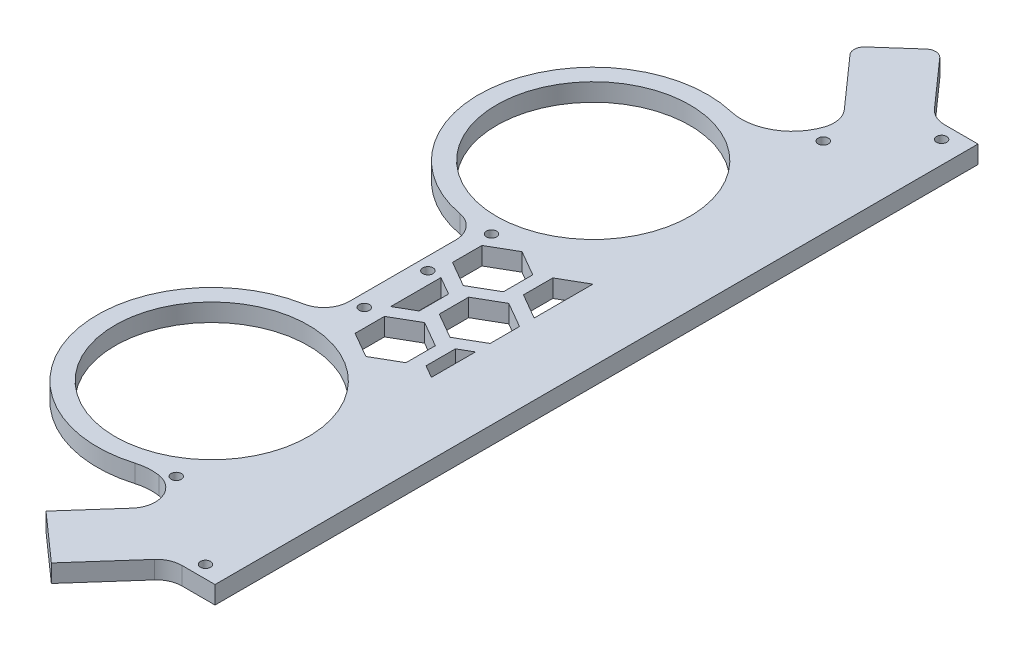
SolidWorks part; units mm, degrees
ref_plane "Front Plane" through (0, 0, 0) normal (0, 0, 1) x (1, 0, 0)
ref_plane "Top Plane" through (0, 0, 0) normal (0, 1, 0) x (1, 0, 0)
ref_plane "Right Plane" through (0, 0, 0) normal (1, 0, 0) x (0, 0, -1)
sketch "Sketch4" plane through (0, 0, 0) normal (0, 1, 0) x (1, 0, 0)
  line L0 (-171.45, -234.95) -> (-171.45, 190.5) construction
  line L1 (-127, -190.5) -> (127, -190.5) construction
  line L2 (-127, -190.5) -> (-127, 190.5) construction
  line L3 (-127, 190.5) -> (127, 190.5) construction
  line L4 (127, -190.5) -> (127, 190.5) construction
  line L5 (-127, -190.5) -> (127, 190.5) construction
  line L6 (-127, 190.5) -> (127, -190.5) construction
  line L8 (171.45, -234.95) -> (171.45, 190.5) construction
  line L9 (-171.45, -234.95) -> (171.45, -234.95) construction
  line L10 (-171.45, 190.5) -> (171.45, 190.5) construction
  line L12 (-171.45, -234.95) -> (-171.45, 234.95) construction
  line L13 (-171.45, 234.95) -> (171.45, 234.95) construction
  line L14 (171.45, -234.95) -> (171.45, 234.95) construction
  point P0 (0, 0)
  dimension "D1" = 254
  dimension "D2" = 381
  dimension "D3" = 44.45
sketch "Sketch5" plane through (0, 0, 0) normal (0, 1, 0) x (1, 0, 0)
  line L16 (-171.45, 190.5) -> (-127, 190.5)
  line L17 (-171.45, -234.95) -> (-171.45, 190.5) construction
  line L18 (-171.45, 190.5) -> (-171.45, -190.5)
  line L19 (-171.45, -190.5) -> (-127, -190.5)
  line L23 (-162.56, 181.61) -> (-162.56, -181.61)
  line L24 (-162.56, -181.61) -> (-135.89, -181.61)
  line L26 (-162.56, 181.61) -> (-135.89, 181.61)
  line L57 (-127, -190.5) -> (-127, 190.5) construction
  line L58 (-135.89, -181.61) -> (-135.89, 181.61) construction
  line L59 (-135.89, 181.61) -> (-135.89, -181.61)
  line L60 (-127, 190.5) -> (-127, -190.5)
  line L61 (-127, 0) -> (-193.675, 0) construction
  line L68 (-149.225, 190.5) -> (-149.225, -190.5) construction
  line L69 (-149.225, 0) -> (-162.56, 181.61) construction
  line L70 (-215.9, 87.2522) -> (-171.45, 87.2522) construction
  line L71 (-215.9, -103.2478) -> (-171.45, -103.2478) construction
  line L72 (-149.225, 0) -> (-135.89, 181.61) construction
  line L73 (-162.56, -181.61) -> (-149.225, 0) construction
  line L74 (-149.225, 0) -> (-135.89, -181.61) construction
  line L75 (-149.225, 166.5793) -> (-191.3669, 214.08) construction
  line L76 (-215.9, 87.2522) -> (-215.9, -103.2478) construction
  line L77 (-215.9, 30.1022) -> (-215.9, -46.0978)
  line L78 (-193.675, -103.2478) -> (-193.675, 87.2522) construction
  line L199 (-149.225, 190.5) -> (-177.199, 222.0312)
  line L740 (-177.199, 222.0312) -> (-200.9493, 200.9602)
  line L741 (-200.9493, 200.9602) -> (-171.45, 167.7098)
  line L742 (-149.225, -190.5) -> (-177.199, -222.0312)
  line L743 (-177.199, -222.0312) -> (-200.9493, -200.9602)
  line L744 (-200.9493, -200.9602) -> (-171.45, -167.7098)
  line L772 (-127, 190.5) -> (-171.45, 190.5) construction
  line L777 (-135.89, 181.61) -> (-162.56, 181.61) construction
  circle A0 centre (-215.9, 87.2522) radius 48.26
  circle A1 centre (-215.9, -103.2478) radius 48.26
  circle A2 centre (-215.9, 87.2522) radius 57.15
  circle A3 centre (-215.9, -103.2478) radius 57.15
  dimension "D2" = 190.5
  dimension "D4" = 96.52
  dimension "D7" = 31.75
  dimension "D5" = 44.45
  dimension "D8" = 15.875
  dimension "D6" = 8.89
  dimension "D3" = 63.5
  dimension "D9" = 44.45
  dimension "D1" = 8.89
extrude "Boss-Extrude1" add sketch "Sketch5" against normal blind 8.89 contours A2 L18 A0 | L18 A2 L23 A0 | A3 L18 L19 L60 L16 A2 L23 L26 L59 L24 | A3 L23 A2 L18 | L18 A3 A1 | L18 A3 L23 A1 | A3 L18 A2 L77 | A3 L23 L24 L59 L26 A2 | L23 A2 | L23 A3 | L744 L743 L742 L19 L18 | L740 L741 L18 L16 L199 region at (-177.2385, 0, -197.9808) region at (-160.3375, 0, -186.6642) region at (-166.8113, 0, -87.2522) region at (-172.9793, 0, -114.6099) region at (-161.0316, 0, -87.2522) region at (-148.9635, 0, -0.1771) region at (-192.0002, 0, 7.9978) region at (-177.2385, 0, 197.9808) region at (-166.8358, 0, 7.9978) region at (-191.9295, 0, 53.0574) region at (-161.0316, 0, 103.2478) region at (-166.8113, 0, 103.2478)
fillet "Fillet1" radius 25.4 2 edges at (-171.45, -4.445, 139.1688) (-171.45, -4.445, -123.1732)
sketch "Sketch9" plane through (0, 0, 0) normal (0, 1, 0) x (1, 0, 0)
  line L0 (-215.9, 30.1022) -> (-215.9, -46.0978) construction
  line L1 (-194.31, 30.1022) -> (-207.01, 22.7699)
  line L2 (-207.01, 22.7699) -> (-207.01, 8.1052)
  line L3 (-207.01, 8.1052) -> (-194.31, 0.7728)
  line L4 (-194.31, 0.7728) -> (-181.61, 8.1052)
  line L5 (-181.61, 8.1052) -> (-181.61, 22.7699)
  line L6 (-181.61, 22.7699) -> (-194.31, 30.1022)
  line L7 (-194.31, 30.1022) -> (-215.9, 30.1022) construction
  line L8 (-203.3451, -1.3431) -> (-203.3451, -26.4406) construction
  line L9 (-162.56, -2.8934) -> (-175.26, 4.439)
  line L10 (-175.26, 4.439) -> (-187.96, -2.8934)
  line L11 (-187.96, -2.8934) -> (-187.96, -17.5581)
  line L12 (-187.96, -17.5581) -> (-175.26, -24.8904)
  line L13 (-175.26, -24.8904) -> (-162.56, -17.5581)
  line L14 (-162.56, -17.5581) -> (-162.56, -2.8934)
  line L16 (-162.56, 33.7684) -> (-175.26, 26.436)
  line L17 (-175.26, 26.436) -> (-175.26, 11.7713)
  line L18 (-175.26, 11.7713) -> (-162.56, 4.439)
  line L21 (-194.31, -6.5595) -> (-203.3451, -1.3431)
  line L25 (-203.3451, -26.4406) -> (-194.31, -21.2242)
  line L26 (-194.31, -21.2242) -> (-194.31, -6.5595)
  line L27 (-203.3451, -1.3431) -> (-203.3451, -26.4406)
  line L28 (-219.71, -13.8919) -> (-219.71, -20.4284) [skipped]
  line L29 (-213.36, -24.8904) -> (-207.6992, -28.1586) [skipped]
  line L30 (-210.6749, -1.3431) -> (-216.3357, -4.6114) [skipped]
  line L31 (-187.96, -24.8904) -> (-200.66, -32.2228)
  line L32 (-200.66, -32.2228) -> (-200.66, -46.8874)
  line L33 (-200.66, -46.8874) -> (-187.96, -54.2198)
  line L34 (-187.96, -54.2198) -> (-175.26, -46.8874)
  line L35 (-175.26, -46.8874) -> (-175.26, -32.2228)
  line L36 (-175.26, -32.2228) -> (-187.96, -24.8904)
  line L37 (-162.56, 33.7684) -> (-162.56, 4.439) construction
  line L38 (-162.56, -24.8904) -> (-168.91, -28.5566)
  line L39 (-168.91, -28.5566) -> (-168.91, -43.2213)
  line L40 (-168.91, -43.2213) -> (-162.56, -46.8874)
  line L44 (-162.56, -24.8904) -> (-162.56, -46.8874) construction
  line L45 (-162.56, 33.7684) -> (-162.56, 4.439)
  line L46 (-149.86, 26.436) -> (-156.21, 30.1022) [skipped]
  line L47 (-149.86, 11.7713) -> (-149.86, 19.1037) [skipped]
  line L48 (-162.56, 4.439) -> (-156.21, 8.1052) [skipped]
  line L49 (-143.51, -28.5566) -> (-149.86, -24.8904) [skipped]
  line L50 (-143.51, -43.2213) -> (-143.51, -35.8889) [skipped]
  line L51 (-156.21, -50.5536) -> (-149.86, -46.8874) [skipped]
  line L52 (-162.56, -24.8904) -> (-162.56, -46.8874)
  line L53 (-138.1125, -190.5) -> (-138.1125, 190.5829) construction
  line L54 (-149.225, -190.5) -> (-127, -190.5) construction
  line L55 (-171.45, 177.8) -> (-127.3047, 177.8) construction
  line L57 (-215.9, 30.1022) -> (-215.9, -46.0978) construction
  circle A0 centre (-194.31, 15.4375) radius 12.7 construction
  circle A1 centre (-175.26, -10.2257) radius 12.7 construction
  arc A2 (-162.56, 31.8037) -> (-162.56, 6.4037) centre (-162.56, 19.1037) ccw construction
  arc A3 (-203.3451, -26.0516) -> (-203.3451, -1.7322) centre (-207.01, -13.8919) ccw construction
  circle A4 centre (-187.96, -39.5551) radius 12.7 construction
  arc A5 (-162.56, -24.8904) -> (-162.56, -46.8874) centre (-156.21, -35.8889) ccw construction
  circle A7 centre (-138.1125, -184.15) radius 2.5527
  circle A9 centre (-183.4361, -153.4326) radius 2.5527
  circle A12 centre (-209.55, -33.3978) radius 2.5527
  circle A13 centre (-209.55, -1.6478) radius 2.5527
  circle A14 centre (-209.55, 30.1022) radius 2.5527
  circle A15 centre (-138.1125, 183.4185) radius 2.5527
  circle A16 centre (-166.9399, 153.1572) radius 2.5527
  point P80 (0, 0)
  dimension "D1" = 25.4
  dimension "D3" = 25.4
  dimension "D6" = 25.4
  dimension "D13" = 6.35
  dimension "D14" = 25.4
  dimension "D16" = 5.1054
  dimension "D17" = 6.35
  dimension "D20" = 6.35
  dimension "D21" = 5.1054
  dimension "D2" = 8.89
  dimension "D4" = 6.35
  dimension "D5" = 6.35
  dimension "D7" = 6.35
  dimension "D8" = 12.7
  dimension "D9" = 6.35
  dimension "D10" = 6.35
  dimension "D11" = 6.35
  dimension "D12" = 6.35
  dimension "D15" = 6.35
  dimension "D19" = 3
extrude "Cut-Extrude1" cut sketch "Sketch9" against normal blind 12.7 contours L5 L6 L1 L2 L3 L4 | L35 L36 L31 L32 L33 L34 | L13 L14 L9 L10 L11 L12 | L21 L27 L25 L26 | L45 L16 L17 L18 | L52 L38 L39 L40 | A9 | A15 | A7 | A16 | A13 | A12 | A14 region at (-194.31, 0, -15.4375) region at (-175.26, 0, 10.2257) region at (-168.2044, 0, -19.1037) region at (-199.2226, 0, 13.8919) region at (-187.96, 0, 39.5551) region at (-165.5233, 0, 35.8889) region at (-138.1125, 0, 184.15) region at (-183.4361, 0, 153.4326) region at (-209.55, 0, 33.3978) region at (-209.55, 0, 1.6478) region at (-209.55, 0, -30.1022) region at (-138.1125, 0, -183.4185) region at (-166.9399, 0, -153.1572)
fillet "Fillet3" radius 12.7 4 edges at (-149.225, -4.445, -190.5) (-171.45, -4.445, -167.7098) (-171.45, -4.445, 167.7098) (-149.225, -4.445, 190.5)
fillet "Fillet4" radius 12.7 2 edges at (-215.9, -4.445, 46.0978) (-215.9, -4.445, -30.1022)
fillet "Fillet5" radius 5.08 2 edges at (-177.199, -4.445, -222.0312) (-200.9493, -4.445, -200.9602)
